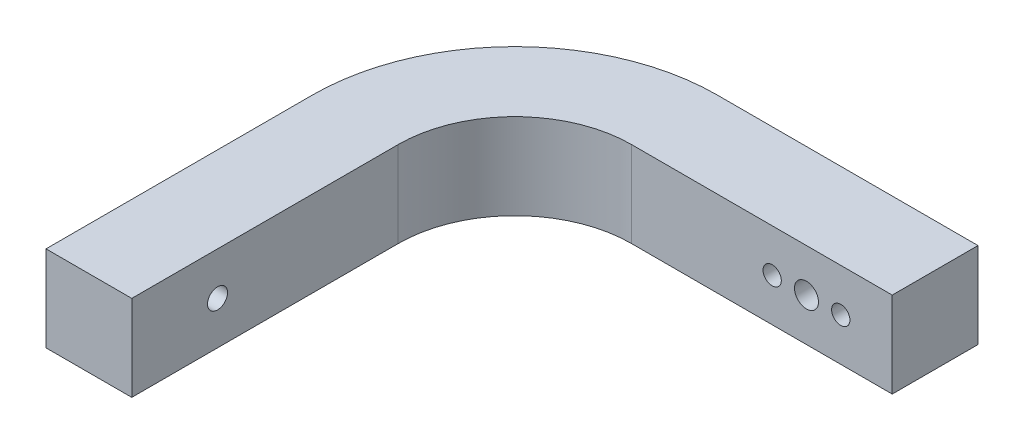
SolidWorks part; units mm, degrees
ref_plane "Front Plane" through (0, 0, 0) normal (0, 0, 1) x (1, 0, 0)
ref_plane "Top Plane" through (0, 0, 0) normal (0, 1, 0) x (1, 0, 0)
ref_plane "Right Plane" through (0, 0, 0) normal (1, 0, 0) x (0, 0, -1)
ref_axis "Z" through (0, 0, -4.1) along (0, 0, 1)
sketch "Sketch1" plane through (0, 0, 0) normal (0, 1, 0) x (1, 0, 0)
  line L0 (-30.6, 0) -> (30.6, 0) construction
  line L1 (-66, -35.4) -> (-66, -82)
  line L2 (-66, -82) -> (-51, -82)
  line L3 (-51, -82) -> (-51, -35.4)
  line L4 (-30.6, -15) -> (30.6, -15) construction
  line L5 (0, -15) -> (0, 0) construction
  line L6 (51, -82) -> (51, -35.4) construction
  line L7 (66, -82) -> (51, -82) construction
  line L8 (66, -35.4) -> (66, -82) construction
  line L9 (30.6, 0) -> (30.6, -15) construction
  line L10 (15, -15) -> (15, 0)
  line L11 (-30.6, -15) -> (15, -15)
  line L12 (-30.6, 0) -> (15, 0)
  line L13 (0, 4.1) -> (0, -86.1) construction
  arc A0 (-30.6, 0) -> (-66, -35.4) centre (-30.6, -35.4) ccw
  arc A1 (-51, -35.4) -> (-30.6, -15) centre (-30.6, -35.4) cw
  arc A2 (51, -35.4) -> (30.6, -15) centre (30.6, -35.4) ccw construction
  arc A3 (30.6, 0) -> (66, -35.4) centre (30.6, -35.4) cw construction
  dimension "D3" = 20.4
  dimension "D1" = 102
  dimension "D2" = 15
  dimension "D4" = 67
  dimension "D5" = 15
extrude "Boss-Extrude1" add sketch "Sketch1" along normal blind 7.5 and the other way blind 7.5
sketch "Sketch2" plane through (-51, 0, 0) normal (-1, 0, 0) x (0, 0, 1)
  line L1 (44.55, 0) -> (-44.55, 0) construction
  line L2 (0, -8.25) -> (0, 8.25) construction
  circle A0 centre (67, 0) radius 1.75
  dimension "D1" = 3.5
  dimension "D2" = 67
extrude "Cut-Extrude1" cut sketch "Sketch2" against normal through all both and the other way through all
ref_axis "Axis2" through (-92.6767, 0, 67) along (1, 0, 0)
sketch "Sketch3" plane through (0, 0, 0) normal (0, 0, -1) x (-1, 0, 0)
  line L0 (-6, 0) -> (6, 0) construction
  circle A0 centre (0, 0) radius 2.1
  circle A1 centre (-6, 0) radius 1.6
  circle A2 centre (6, 0) radius 1.6
  dimension "D1" = 4.2
  dimension "D3" = 3.2
  dimension "D2" = 12
extrude "Cut-Extrude2" cut sketch "Sketch3" against normal through all
sketch "Sketch4" plane through (-66, 0, 0) normal (1, 0, 0) x (0, 0, -1)
  circle A0 centre (-67, 0) radius 2.275
  circle A1 centre (-67, 0) radius 1.75 construction
  dimension "D1" = 4.55
extrude "Cut-Extrude3" cut sketch "Sketch4" along normal blind 6
sketch "Sketch5" plane through (-66, 0, 0) normal (-1, 0, 0) x (0, 0, 1)
  circle A0 centre (67, 0) radius 3.825
  dimension "D1" = 7.65
extrude "Cut-Extrude4" cut sketch "Sketch5" against normal blind 0.75
equation "\"width\"= \"EyeDiameter\" + \"EyeClearance\""
equation "\"prongwidth\"= \"L2Thickness\""
equation "\"D2@Sketch1\"=\"prongwidth\""
equation "\"D3@Sketch1\"=\"width\"/5"
equation "\"pronglength\"= \"BasePlaneDistance\"'model implicitly adds clearance (of prongwidth) to the hole drilled at the baseplanedistance"
equation "\"D4@Sketch1\"=\"pronglength\""
equation "\"D1@Boss-Extrude1\"=\"prongwidth\"/2"
equation "\"D2@Boss-Extrude1\"=\"prongwidth\"/2"
equation "\"lbracket-plane-to-axis\"= \"BasePlaneDistance\""
equation "\"D2@Sketch2\"=\"lbracket-plane-to-axis\""
equation "\"EyeDiameter\" = 100"
equation "\"BasePlaneDistance\" = \"EyeDiameter\"/2+\"L2Thickness\"+\"EyeClearance\""
equation "\"EyeClearance\" = 2"
equation "\"D1@Sketch1\"=\"EyeDiameter\"+\"EyeClearance\""
equation "\"BearingDepth\"= 6"
equation "\"BearingHousingID\"=4.5"
equation "\"D1@Sketch4\"=\"BearingHousingID\" + \"PrinterFilamentThickness\" * \"ApplyPrinterOffset\" / 2"
equation "\"D1@Cut-Extrude3\"=\"BearingDepth\""
equation "\"BearingFlangeThickness\"= 0.75"
equation "\"BearingFlangeOD\"=7.5"
equation "\"D1@Sketch5\"=\"BearingFlangeOD\" + \"PrinterFilamentThickness\"*1.5 *\"ApplyPrinterOffset\""
equation "\"D1@Cut-Extrude4\"=\"BearingFlangeThickness\""
equation "\"PrinterFilamentThickness\"= 0.1"
equation "\"ApplyPrinterOffset\"= 1'if 1, adjust hole sizes to try and make pressfits work with the 3d printer"
equation "\"L2Thickness\" = 15"
equation "\"L2_ID\" = 20"
equation "\"vx\" = 0"
equation "\"vy\" = 0"
equation "\"vz\" = 100"
equation "\"parametric_end\" = 1"
equation "\"Rw_3_xx\" = -(\"vz\")/sqr((\"vx\")^2 + (\"vz\")^2)"
equation "\"Rw_3_xy\" = 0"
equation "\"Rw_3_xz\" = (\"vx\")/sqr((\"vx\")^2 + (\"vz\")^2)"
equation "\"Rw_3_zx\" = (\"vx\")/sqr((\"vx\")^2 + (\"vy\")^2 + (\"vz\")^2)"
equation "\"Rw_3_zy\" = (\"vy\")/sqr((\"vx\")^2 + (\"vy\")^2 + (\"vz\")^2)"
equation "\"Rw_3_zz\" = (\"vz\")/sqr((\"vx\")^2 + (\"vy\")^2 + (\"vz\")^2)"
equation "\"Rw_3_yx\" = (\"vx\")*(\"vy\")/sqr((\"vx\")^4 + (\"vx\")^2*(\"vy\")^2 + 2*(\"vx\")^2*(\"vz\")^2 + (\"vy\")^2*(\"vz\")^2 + (\"vz\")^4)"
equation "\"Rw_3_yy\" = -sqr((\"vx\")^2 + (\"vz\")^2)/sqr((\"vx\")^2 + (\"vy\")^2 + (\"vz\")^2)"
equation "\"Rw_3_yz\" = (\"vy\")*(\"vz\")/sqr((\"vx\")^4 + (\"vx\")^2*(\"vy\")^2 + 2*(\"vx\")^2*(\"vz\")^2 + (\"vy\")^2*(\"vz\")^2 + (\"vz\")^4)"
equation "\"O2Targx\" = -\"BasePlaneDistance\"*(\"vx\")*(\"vy\")/sqr((\"vx\")^4 + (\"vx\")^2*(\"vy\")^2 + 2*(\"vx\")^2*(\"vz\")^2 + (\"vy\")^2*(\"vz\")^2 + (\"vz\")^4)"
equation "\"O2Targy\" = \"BasePlaneDistance\"*sqr((\"vx\")^2 + (\"vz\")^2)/sqr((\"vx\")^2 + (\"vy\")^2 + (\"vz\")^2)"
equation "\"O2Targz\" = -\"BasePlaneDistance\"*(\"vy\")*(\"vz\")/sqr((\"vx\")^4 + (\"vx\")^2*(\"vy\")^2 + 2*(\"vx\")^2*(\"vz\")^2 + (\"vy\")^2*(\"vz\")^2 + (\"vz\")^4)"
equation "\"O2Targx_0\" = -(\"BasePlaneDistance\")*sqr((\"vx\")^2 + (\"vz\")^2)/sqr((\"vx\")^2 + (\"vy\")^2 + (\"vz\")^2)"
equation "\"O2Targy_0\" = -(\"BasePlaneDistance\")*(\"vy\")*(\"vz\")/sqr((\"vx\")^4 + (\"vx\")^2*(\"vy\")^2 + 2*(\"vx\")^2*(\"vz\")^2 + (\"vy\")^2*(\"vz\")^2 + (\"vz\")^4)"
equation "\"O2Targz_0\" = (\"BasePlaneDistance\")*(\"vx\")*(\"vy\")/sqr((\"vx\")^4 + (\"vx\")^2*(\"vy\")^2 + 2*(\"vx\")^2*(\"vz\")^2 + (\"vy\")^2*(\"vz\")^2 + (\"vz\")^4) + (\"BasePlaneDistance\")"
equation "\"theta2_s1\" = arcsin(((\"BasePlaneDistance\") - (\"O2Targz_0\"))/(\"BasePlaneDistance\")) + pi"
equation "\"theta2_s2\" = -arcsin(((\"BasePlaneDistance\") - (\"O2Targz_0\"))/(\"BasePlaneDistance\"))"
equation "\"theta1_s1\" = arcsin((\"O2Targy_0\")/((\"BasePlaneDistance\")*cos((\"Theta2\")))) + pi"
equation "\"theta1_s2\" = -arcsin((\"O2Targy_0\")/((\"BasePlaneDistance\")*cos((\"Theta2\"))))"
equation "\"theta1_s3\" = -arccos(-(\"O2Targx_0\")/((\"BasePlaneDistance\")*cos((\"Theta2\")))) + 2*pi"
equation "\"theta1_s4\" = arccos(-(\"O2Targx_0\")/((\"BasePlaneDistance\")*cos((\"Theta2\"))))"
equation "\"Theta1\" = \"theta1_s2\" 'so far, theta1_s1 and theta1_s4 have agreed, and they agree with the sw constraint solver"
equation "\"Theta2\" = \"theta2_s2\""
equation "\"o2_x\" = -(\"BasePlaneDistance\")*cos((\"Theta1\"))*cos((\"Theta2\"))"
equation "\"o2_y\" = -(\"BasePlaneDistance\")*sin((\"Theta1\"))*cos((\"Theta2\"))"
equation "\"o2_z\" = (\"BasePlaneDistance\")*(sin((\"Theta2\")) + 1)"
equation "\"o1_x\" = (\"BasePlaneDistance\")*sin((\"Theta1\"))"
equation "\"o1_y\" = -(\"BasePlaneDistance\")*cos((\"Theta1\"))"
equation "\"o1_z\" = (\"BasePlaneDistance\")"
equation "\"Actuator1_Theta\" = atn(\"vx\"/\"vz\") 'ik solution for the single link joint"
equation "\"Actuator2_Theta\" = \"Theta1\"  'ik solution for the double link joint"
